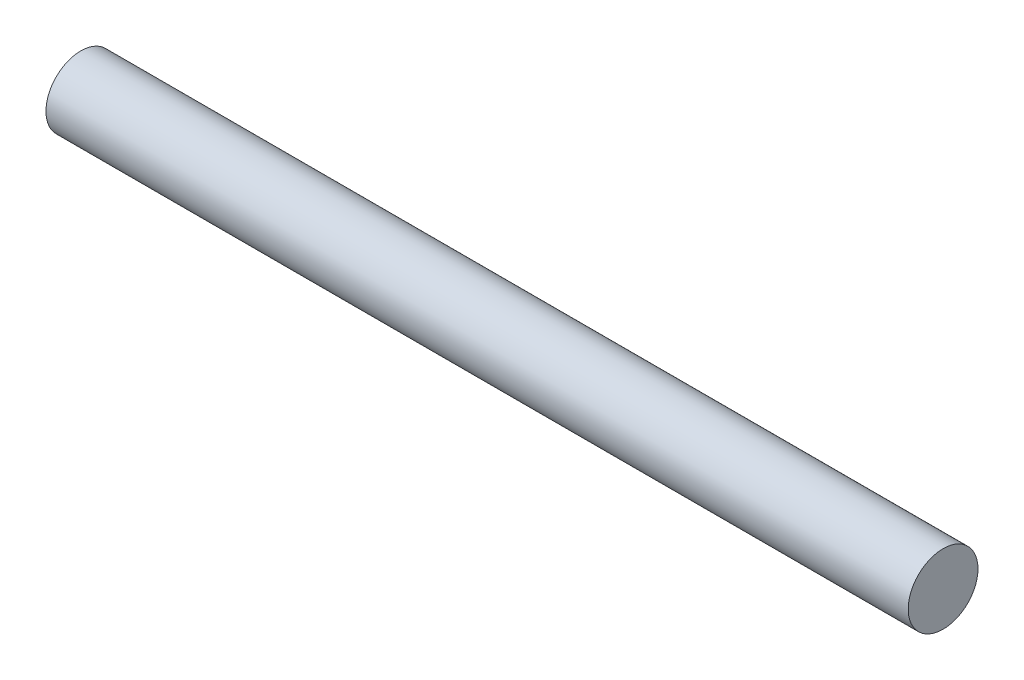
SolidWorks part; units mm, degrees
ref_plane "Front Plane" through (0, 0, 0) normal (0, 0, 1) x (1, 0, 0)
ref_plane "Top Plane" through (0, 0, 0) normal (0, 1, 0) x (1, 0, 0)
ref_plane "Right Plane" through (0, 0, 0) normal (1, 0, 0) x (0, 0, -1)
sketch "Sketch1" plane through (0, 0, 0) normal (1, 0, 0) x (0, 0, -1)
  circle A0 centre (0, 0) radius 21.59
  dimension "D1" = 43.18
extrude "Boss-Extrude1" add sketch "Sketch1" along normal blind 533.4
